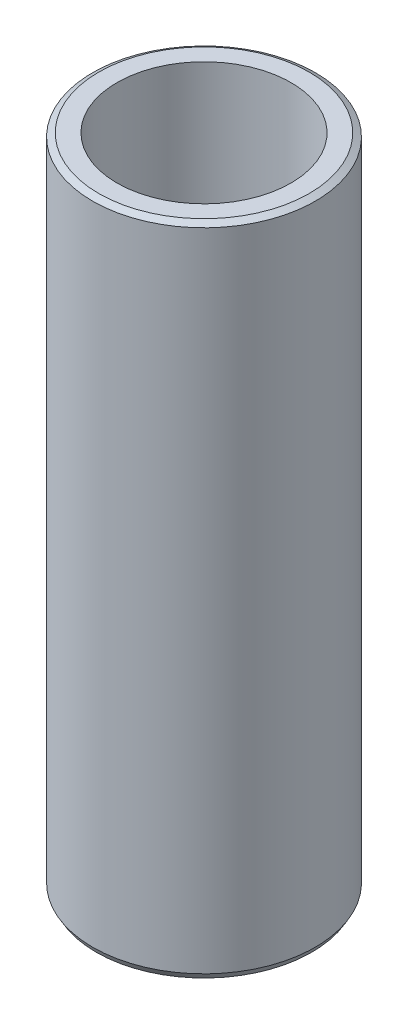
SolidWorks part; units mm, degrees
ref_plane "Front Plane" through (0, 0, 0) normal (0, 0, 1) x (1, 0, 0)
ref_plane "Top Plane" through (0, 0, 0) normal (0, 1, 0) x (1, 0, 0)
ref_plane "Right Plane" through (0, 0, 0) normal (1, 0, 0) x (0, 0, -1)
sketch "Sketch1" plane through (0, 0, 0) normal (0, 1, 0) x (1, 0, 0)
  circle A0 centre (0, 0) radius 45
  dimension "SHAFT_OD" = 90
extrude "Boss-Extrude1" add sketch "Sketch1" along normal blind 265.0019
sketch "Sketch2" plane through (0, 0, 0) normal (0, 1, 0) x (1, 0, 0)
  circle A0 centre (0, 0) radius 35.1724
  dimension "BORE_D" = 70.3448
extrude "Cut-Extrude1" cut sketch "Sketch2" along normal through all
chamfer "Chamfer1" distance 1.4333 angle 60 2 edges at (0, 265.0019, 45) (0, 0, 45) first distance on face at (0, 265.0019, 45) first distance on face at (0, 0, 35.1724)
